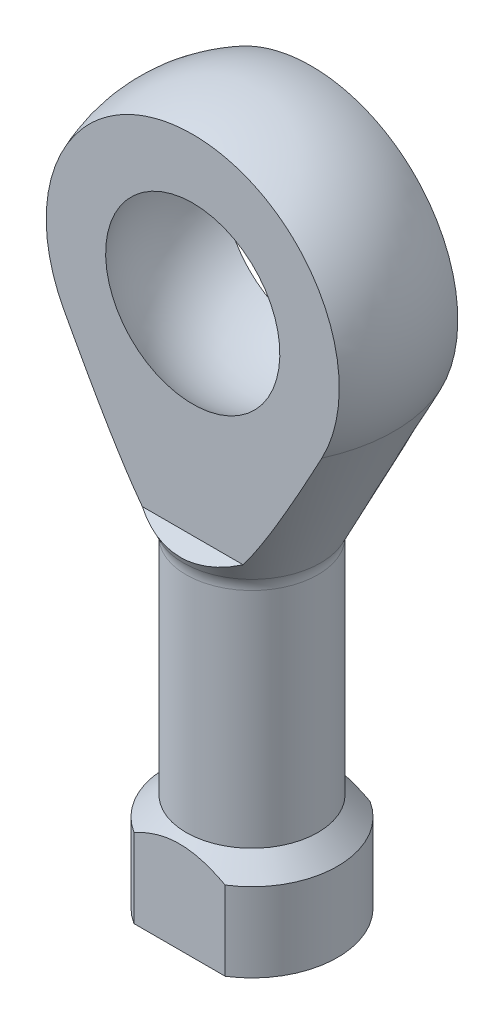
SolidWorks part; units mm, degrees
material "不锈钢 (铁素体)"
ref_plane "前视基准面" through (0, 0, 0) normal (0, 0, 1) x (1, 0, 0)
ref_plane "上视基准面" through (0, 0, 0) normal (0, 1, 0) x (1, 0, 0)
ref_plane "右视基准面" through (0, 0, 0) normal (1, 0, 0) x (0, 0, -1)
sketch "草图2" plane through (0, 0, 0) normal (0, 0, 1) x (1, 0, 0)
  line L0 (0, 35.781) -> (0, -42.5853) construction
  line L1 (3.25, 0) -> (-3.25, 0)
  line L2 (-3.25, 0) -> (-3.25, 3)
  line L3 (-2.5, 3.7337) -> (-2.5, 12.2079)
  line L4 (3.25, 0) -> (3.25, 3)
  line L5 (3.25, 3) -> (2.5, 3.7337)
  line L6 (2.5, 3.7337) -> (2.5, 12.2079)
  line L7 (5.3928, 18.3698) -> (2.6012, 12.6462)
  line L8 (-3.25, 3) -> (-2.5, 3.7337)
  line L9 (-5.3928, 18.3698) -> (-2.6012, 12.6462)
  arc A0 (5.3928, 18.3698) -> (-5.3928, 18.3698) centre (0, 21) ccw
  arc A1 (2.6012, 12.6462) -> (2.5, 12.2079) centre (3.5, 12.2079) ccw
  arc A3 (-2.6012, 12.6462) -> (-2.5, 12.2079) centre (-3.5, 12.2079) cw
  point P9 (0, 0)
  point P11 (0, 0)
  dimension "D6" = 6
  dimension "D2" = 3.25
  dimension "D8" = 1
  dimension "D1" = 2.5
  dimension "D3" = 3
  dimension "D5" = 21
  dimension "D7" = 26
revolve "旋转3" add sketch "草图2" angle 360 about L0 region at (-2.0948, 15.2462, 0)
sketch "草图3" plane through (0, 0, 0) normal (1, 0, 0) x (0, 0, -1)
  line L0 (0, 25) -> (0, 17)
  arc A0 (0, 25) -> (0, 17) centre (0, 21) ccw
revolve "切除-旋转1" cut sketch "草图3" angle 360 about L0
sketch "草图5" plane through (0, 0, 0) normal (0, -1, 0) x (1, 0, 0)
  circle A0 centre (0, 0) radius 1.5
extrude "切除-拉伸2" cut sketch "草图5" against normal blind 10
sketch "草图6" plane through (0, 0, 0) normal (1, 0, 0) x (0, 0, -1)
  line L0 (2.25, 28.4324) -> (2.25, 13.3698)
  line L1 (2.25, 13.3698) -> (10.25, 5.3698)
  line L2 (10.25, 5.3698) -> (10.25, 28.4324)
  line L3 (10.25, 28.4324) -> (2.25, 28.4324)
  line L4 (0, 29.6854) -> (0, 14.6314) construction
  line L6 (-5.3928, 18.3698) -> (5.3928, 18.3698) construction
  dimension "D1" = 4.5
  dimension "D2" = 8
  dimension "D3" = 135
  dimension "D4" = 5
extrude "切除-拉伸3" cut sketch "草图6" against normal blind 10 and the other way blind 10
mirror "镜向1" about plane through (0, 0, 0) normal (0, 0, 1) of "切除-拉伸3"
ref_plane "基准面1" through (0, 0, 2.75) normal (0, 0, 1) x (1, 0, 0)
sketch "草图7" plane through (0, 0, 2.75) normal (0, 0, 1) x (1, 0, 0)
  line L0 (-3.25, 3) -> (-3.25, 0) construction
  line L1 (-3.25, 3.8047) -> (3.25, 3.8047)
  line L2 (-3.25, 3.8047) -> (-3.25, 0)
  line L3 (-3.25, 0) -> (3.25, 0)
  line L4 (3.25, 3.8047) -> (3.25, 0)
extrude "切除-拉伸4" cut sketch "草图7" along normal through all
mirror "镜向2" about plane through (0, 0, 0) normal (0, 0, 1) of "切除-拉伸4"
